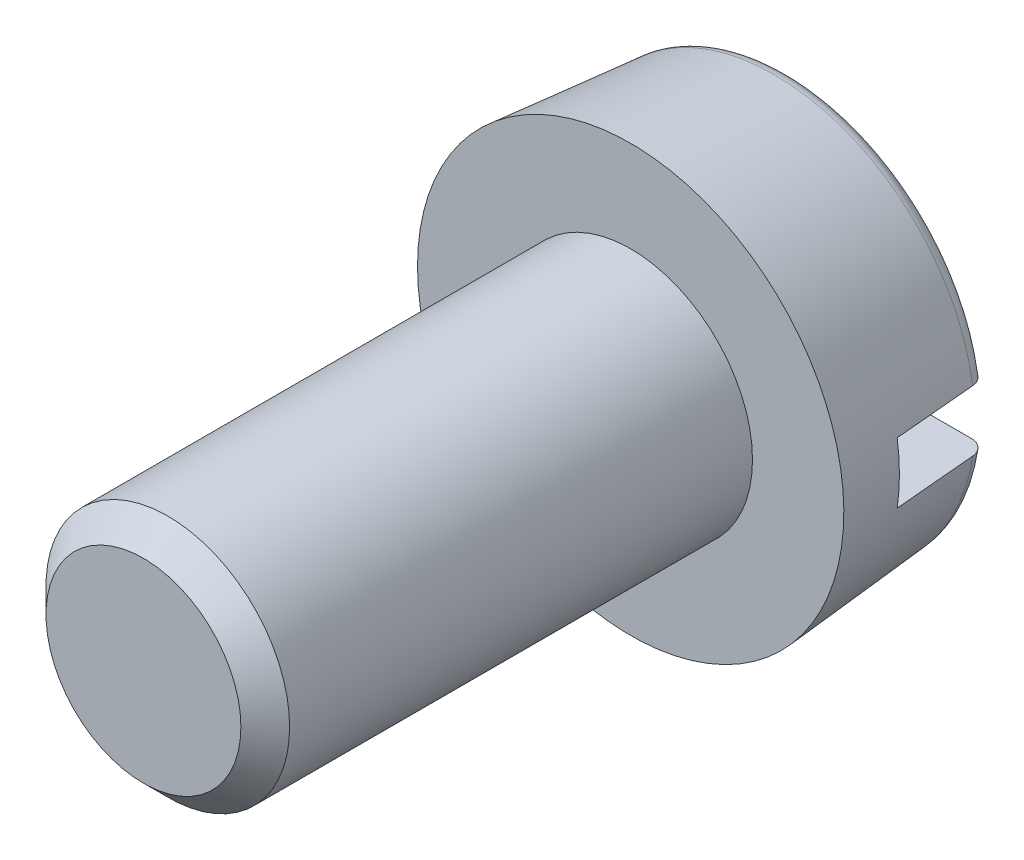
SolidWorks part; units mm, degrees
material "Acier allié"
ref_plane "Plan1" through (0, 0, 0) normal (0, 0, 1) x (1, 0, 0)
ref_plane "Plan2" through (0, 0, 0) normal (0, 1, 0) x (1, 0, 0)
ref_plane "Plan3" through (0, 0, 0) normal (1, 0, 0) x (0, 0, -1)
ref_axis "Z Axis" through (0, 0, -50) along (0, 0, 1)
sketch "Esquisse1" plane through (0, 0, 0) normal (0, 1, 0) x (1, 0, 0)
  line L0 (0, 0) -> (0, 2.6) construction
  line L1 (0, 0) -> (3.5, 0)
  line L2 (0, 0) -> (0, 2.6)
  line L3 (0, 2.6) -> (3.0343, 2.6)
  line L5 (3.5, 0) -> (3.2933, 2.3627)
  arc A0 (3.0343, 2.6) -> (3.2933, 2.3627) centre (3.0343, 2.34) cw
  dimension "D3" = 0.26
  dimension "D1" = 3.5
  dimension "D2" = 2.6
  dimension "D4" = 5
revolve "Base-Révolution" add sketch "Esquisse1" angle 360 about L0 reverse direction yes
sketch "Esquisse2" plane through (0, 0, -2.6) normal (0, 0, 1) x (1, 0, 0)
  line L1 (-3.5, 0.5) -> (3.5, 0.5)
  line L2 (-3.5, 0.5) -> (-3.5, -0.5)
  line L3 (-3.5, -0.5) -> (3.5, -0.5)
  line L4 (3.5, 0.5) -> (3.5, -0.5)
  circle A0 centre (0, 0) radius 3.5 construction
  dimension "D1" = 0.5
extrude "Enlev. mat.-Extru.1" cut sketch "Esquisse2" along normal blind 1.6
sketch "Esquisse3" plane through (0, 0, 0) normal (0, 1, 0) x (1, 0, 0)
  line L1 (0, 0) -> (0, -8) construction
  line L2 (0, 0) -> (2, 0)
  line L3 (0, 0) -> (0, -8)
  line L4 (0, -8) -> (2, -8)
  line L6 (2, 0) -> (2, -8)
  dimension "D1" = 8
  dimension "D2" = 2
revolve "Boss.-Révol.1" add sketch "Esquisse3"
cosmetic thread "Représentation de filetage1" [suppressed]
chamfer "Chanfrein1" distance 0.4 angle 45 1 edges at (2, 0, 8)
sketch "Esquisse4" plane through (0, 0, 0) normal (0, 1, 0) x (1, 0, 0)
  line L0 (1.573, -8.0427) -> (1.573, -7.9573)
  line L2 (1.573, -7.9573) -> (2.0427, -7.6861)
  line L3 (1.573, -8.0427) -> (2.0427, -8.3139)
  line L4 (2.0427, -7.6861) -> (2.0427, -8.3139)
  line L6 (2, 0) -> (2, -8) construction
  line L7 (0, -8) -> (2, -8) construction
  point P4 (2, -8)
  dimension "D2" = 0.0427
  dimension "D3" = 0.0427
  dimension "D4" = 0.4697
  dimension "D5" = 60
  dimension "D1" = 0.427
  dimension "D6" = 60
sketch "Esquisse5" plane through (0, 0, 8) normal (0, 0, 1) x (1, 0, 0)
  circle A0 centre (0, 0) radius 2 construction
  circle A1 centre (0, 0) radius 2
curve "Hélice1" pitch 0.7 height 9.72 turns 13.8857
sweep "Enlèvement de matière-Balayage1" [suppressed] cut profiles "Esquisse4" path "Hélice1"
equation "\"D3@Esquisse1\"=\"D2@Esquisse1\"/10"
equation "\"D1@Chanfrein1\"=\"D2@Esquisse3\"*0.2"
equation "\"D3@Esquisse4\"=0.1*\"D1@Esquisse4\""
equation "\"D4@Esquisse4\"=1.1*\"D1@Esquisse4\""
equation "\"D2@Esquisse4\"=0.1*\"D1@Esquisse4\""
equation "\"D1@Esquisse4\"=0.61*\"D4@Hélice1\""
equation "\"D1@Représentation de filetage1\"=\"D3@Hélice1\""
equation "\"D2@Représentation de filetage1\"=\"D2@Esquisse3\"*1.6"
